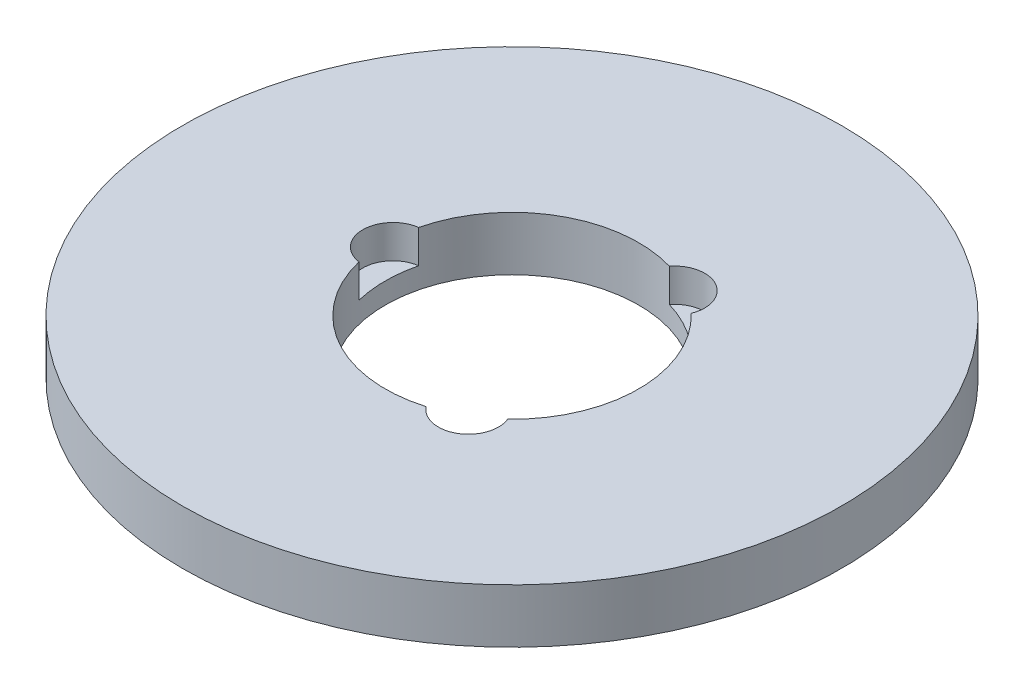
SolidWorks part; units mm, degrees
ref_plane "Front Plane" through (0, 0, 0) normal (0, 0, 1) x (1, 0, 0)
ref_plane "Top Plane" through (0, 0, 0) normal (0, 1, 0) x (1, 0, 0)
ref_plane "Right Plane" through (0, 0, 0) normal (1, 0, 0) x (0, 0, -1)
sketch "Sketch1" plane through (0, 0, 0) normal (0, 1, 0) x (1, 0, 0)
  circle A0 centre (0, 0) radius 97.5
  dimension "FLANGE_OD" = 195
extrude "Boss-Extrude1" add sketch "Sketch1" along normal blind 16
sketch "Sketch2" plane through (0, 0, 0) normal (0, 1, 0) x (1, 0, 0)
  circle A0 centre (0, 0) radius 37.5
  dimension "BORE_D" = 75
extrude "Cut-Extrude1" cut sketch "Sketch2" along normal through all
sketch "Sketch3" plane through (0, 16, 0) normal (0, 1, 0) x (1, 0, 0)
  circle A0 centre (0, 0) radius 35.2172 construction
  circle A1 centre (-35.2172, 0) radius 8.9116
  dimension "BOLT_D" = 17.8232
  dimension "BOLT_PCD" = 70.4345
extrude "Cut-Extrude2" cut sketch "Sketch3" against normal blind 9.8137
pattern_circular "CirPattern1" count 3 over 360 about axis through (0, 0, 0) along (0, 1, 0) of "Cut-Extrude2"
